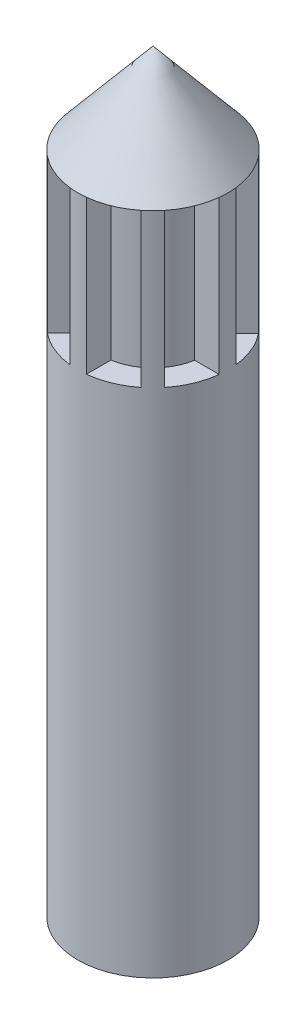
SolidWorks part; units mm, degrees
ref_plane "Front Plane" through (0, 0, 0) normal (0, 0, 1) x (1, 0, 0)
ref_plane "Top Plane" through (0, 0, 0) normal (0, 1, 0) x (1, 0, 0)
ref_plane "Right Plane" through (0, 0, 0) normal (1, 0, 0) x (0, 0, -1)
sketch "Sketch1" plane through (0, 0, 0) normal (0, 1, 0) x (1, 0, 0)
  line L0 (4.9829, 5.7264) -> (3.2807, 4.0242)
  line L1 (-0.4158, 7.3073) -> (-0.4158, 4.9)
  line L2 (1.1995, 7.3036) -> (1.1995, 4.9)
  line L3 (-0.4158, 7.3073) -> (1.1995, 4.9) construction
  line L4 (-0.4158, 4.9) -> (1.1995, 7.3036) construction
  line L5 (6.1226, 4.5816) -> (4.4229, 2.882)
  line L6 (7.6826, 0.7911) -> (5.2753, 0.7911)
  line L7 (7.6789, -0.8243) -> (5.2753, -0.8243)
  line L8 (6.1017, -4.6077) -> (4.3995, -2.9054)
  line L9 (4.9569, -5.7473) -> (3.2572, -4.0477)
  line L10 (1.1663, -7.3073) -> (1.1663, -4.9)
  line L11 (-0.449, -7.3036) -> (-0.449, -4.9)
  line L12 (-4.2324, -5.7264) -> (-2.5302, -4.0242)
  line L13 (-5.372, -4.5816) -> (-3.6724, -2.882)
  line L14 (-6.932, -0.7911) -> (-4.5247, -0.7911)
  line L15 (-6.9284, 0.8243) -> (-4.5247, 0.8243)
  line L16 (-5.3512, 4.6077) -> (-3.6489, 2.9054)
  line L17 (-4.2063, 5.7473) -> (-2.5067, 4.0477)
  circle A0 centre (0.3753, 0) radius 7.35
  circle A1 centre (0.3753, 0) radius 4.9688
  point P2 (0.3925, 6.1027)
  point P36 (0.3753, 0)
extrude "Boss-Extrude1" add sketch "Sketch1" along normal mid plane 15 contours A1 | A1 L5 A0 L0 | A1 L7 A0 L6 | A1 L9 A0 L8 | A1 L11 A0 L10 | A1 L13 A0 L12 | A1 L15 A0 L14 | A1 L17 A0 L16 | A1 L2 A0 L1 region at (4.7294, 0, -4.3305) region at (0.3753, 0, 0) region at (0.392, 0, -6.141) region at (6.5162, 0, 0.0167) region at (-3.9552, 0, -4.3541) region at (4.7058, 0, 4.3541) region at (-5.7657, 0, -0.0167) region at (0.3586, 0, 6.141) region at (-3.9789, 0, 4.3305)
extrude "Boss-Extrude2" add sketch "Sketch1<3>" along normal blind 10 draft 40 from surface contours A0 starting at face at (0.3753, 7.5, 0)
sketch "Sketch1<3>" plane through (0, 0, 0) normal (0, 1, 0) x (1, 0, 0) same geometry as "Sketch1"
extrude "Boss-Extrude3" add sketch "Sketch1<7>" against normal blind 50 from surface contours A0 starting at face at (0.3753, -7.5, 0)
sketch "Sketch1<7>" plane through (0, 0, 0) normal (0, 1, 0) x (1, 0, 0) same geometry as "Sketch1"
